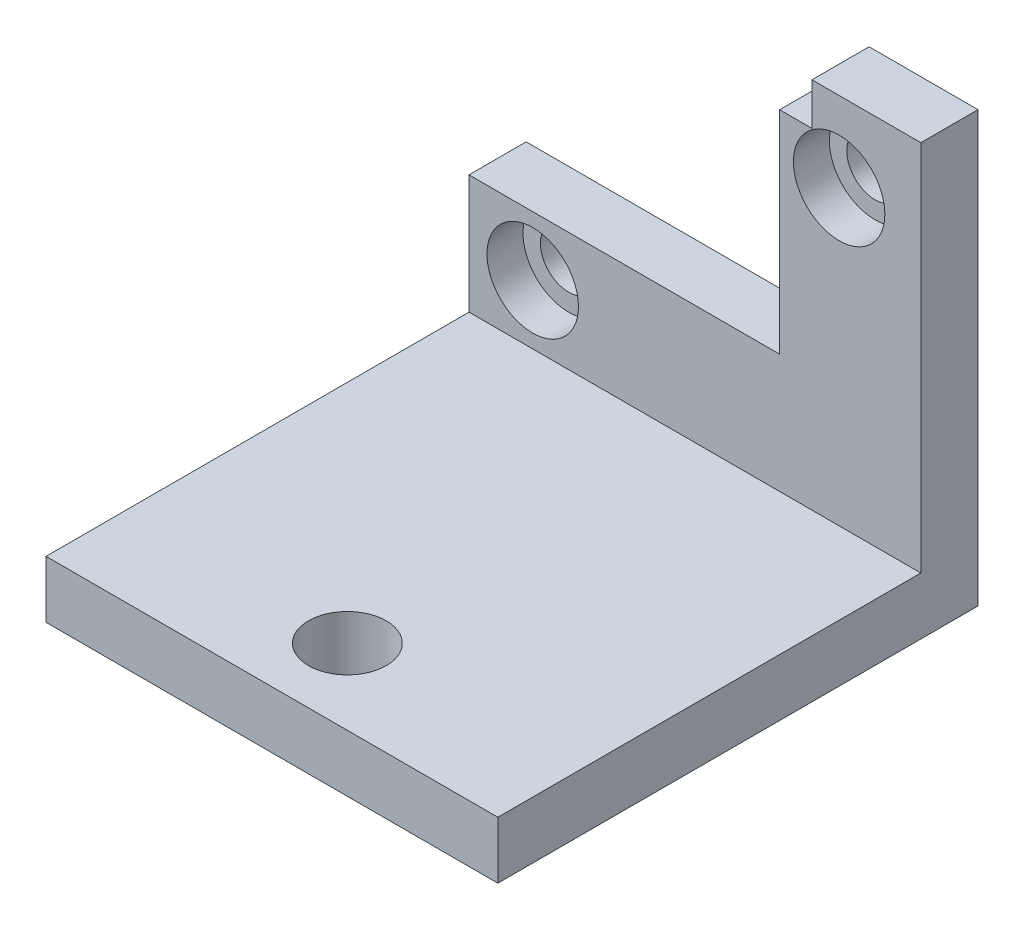
SolidWorks part; units mm, degrees
ref_plane "Front Plane" through (0, 0, 0) normal (0, 0, 1) x (1, 0, 0)
ref_plane "Top Plane" through (0, 0, 0) normal (0, 1, 0) x (1, 0, 0)
ref_plane "Right Plane" through (0, 0, 0) normal (1, 0, 0) x (0, 0, -1)
sketch "Sketch2" plane through (0, 0, 0) normal (0, 0, 1) x (1, 0, 0)
  line L0 (4.3952, 7.8274) -> (4.3952, -1.4384)
  line L1 (4.3952, -1.4384) -> (-11.8608, -1.4384)
  line L2 (-11.8608, -1.4384) -> (-11.8608, -8.0424)
  line L3 (-11.8608, -8.0424) -> (12.2372, -8.0424)
  line L4 (12.2372, -8.0424) -> (12.2372, 12.6586)
  line L5 (12.2372, 12.6586) -> (7.6972, 12.6586)
  line L7 (7.6972, 12.6586) -> (6.1882, 12.6586)
  line L8 (-11.8608, -1.4384) -> (-12.8608, -1.4384)
  line L9 (-11.8608, -1.4384) -> (-11.8608, -8.0424)
  line L10 (-11.8608, -8.0424) -> (-12.8608, -8.0424)
  line L11 (-12.8608, -1.4384) -> (-12.8608, -8.0424)
  line L12 (4.3952, 10.3218) -> (4.3952, 7.8274)
  line L13 (4.3952, 10.3218) -> (6.1882, 10.3218)
  line L14 (6.1882, 10.3218) -> (6.1882, 12.6586)
  circle A0 centre (7.6972, 8.2136) radius 1.5748
  circle A1 centre (-9.3208, -4.7404) radius 1.5748
  point P0 (6.4597, 9.1875)
  dimension "D5" = 4.445
  dimension "D7" = 3.1496
  dimension "D9" = 3.1496
  dimension "D1" = 1
  dimension "D2" = 3.302
  dimension "D3" = 3.302
  dimension "D4" = 24.098
  dimension "D6" = 2.54
  dimension "D8" = 17.018
  dimension "D10" = 14.097
extrude "Boss-Extrude1" add sketch "Sketch2" along normal blind 3.175 contours A0 | L8 L11 L10 L2 | L3 L4 L5 L7 L14 L13 L12 L0 L1 L2 | A1 region at (-12.3608, -4.7404, 0) region at (7.6972, 8.2136, 0)
sketch "Sketch3" plane through (0, 0, 0) normal (0, 0, -1) x (-1, 0, 0)
  line L6 (-12.2372, -8.0424) -> (12.8608, -8.0424)
  line L7 (-12.2372, -8.0424) -> (-12.2372, -11.2174)
  line L8 (-12.2372, -11.2174) -> (12.8608, -11.2174)
  line L9 (12.8608, -8.0424) -> (12.8608, -11.2174)
  dimension "D1" = 3.175
extrude "Boss-Extrude3" add sketch "Sketch3" against normal blind 26.67
sketch "Sketch4" plane through (0, -11.2174, 0) normal (0, -1, 0) x (1, 0, 0)
  line L1 (-0.3118, 26.67) -> (-0.3118, 3.0754) construction
  line L2 (12.2372, 26.67) -> (-12.8608, 26.67) construction
  circle A0 centre (-0.3118, 22.479) radius 2.159
  dimension "D1" = 4.318
  dimension "D2" = 4.191
sketch "Sketch5" plane through (0, 0, 3.175) normal (0, 0, 1) x (1, 0, 0)
  circle A0 centre (7.6972, 8.2136) radius 2.54
  circle A1 centre (-9.3208, -4.7404) radius 2.54
  dimension "D1" = 5.08
  dimension "D2" = 5.08
extrude "Cut-Extrude2" cut sketch "Sketch5" against normal blind 2
extrude "Cut-Extrude3" cut sketch "Sketch4" against normal through all
